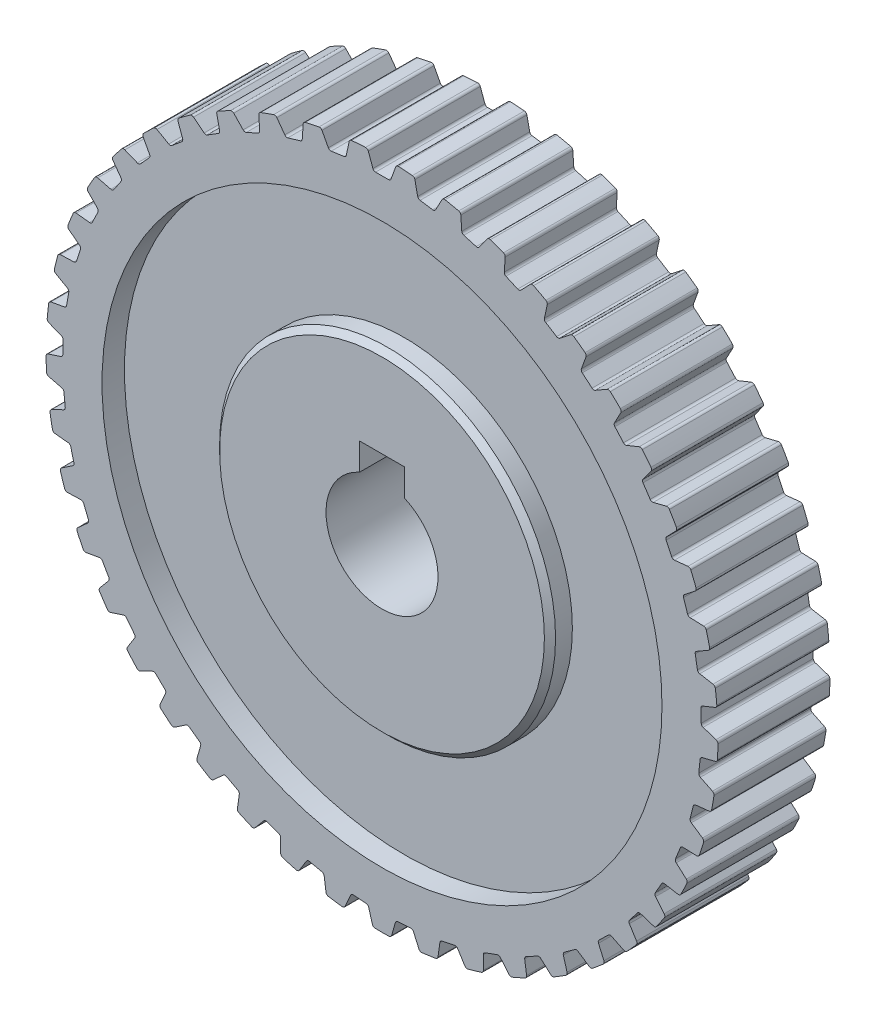
SolidWorks part; units mm, degrees
material "Alloy Steel (SS)"
ref_plane "Front " through (0, 0, 0) normal (0, 0, 1) x (1, 0, 0)
ref_plane "Top " through (0, 0, 0) normal (0, 1, 0) x (1, 0, 0)
ref_plane "Right " through (0, 0, 0) normal (1, 0, 0) x (0, 0, -1)
sketch "Sketch1" plane through (0, 0, 0) normal (0, 0, 1) x (1, 0, 0)
  line L0 (0, 0) -> (0, 14.3078) construction
  line L2 (2, 7) -> (-2, 7)
  line L3 (2, 7) -> (2, 4.5826)
  line L5 (-2, 7) -> (-2, 4.5826)
  circle A0 centre (0, 0) radius 30
  arc A1 (-2, 4.5826) -> (2, 4.5826) centre (0, 0) ccw
  dimension "D1" = 60
  dimension "D2" = 10
  dimension "D3" = 4
  dimension "D4" = 7
extrude "Boss-Extrude1" add sketch "Sketch1" along normal blind 10
sketch "Sketch2" plane through (0, 0, 10) normal (0, 0, 1) x (1, 0, 0)
  line L0 (0, 0) -> (0, 30) construction
  line L1 (-0.75, 28.5) -> (0.75, 28.5)
  line L2 (0.75, 28.5) -> (1.2859, 29.9724)
  line L3 (-0.75, 28.5) -> (-1.2859, 29.9724)
  circle A0 centre (0, 0) radius 30 construction
  circle A1 centre (0, 0) radius 30
  circle M5 centre (0, 0) radius 30
  dimension "D1" = 20
  dimension "D2" = 20
  dimension "D3" = 1.5
  dimension "D4" = 28.5
extrude "Cut-Extrude1" cut sketch "Sketch2" against normal through all contours L1 L0 A1 L3 | L0 L1 L2 M5 region at (-0.5201, 29.3114, 10) region at (0.5201, 29.3114, 10)
pattern_circular "CirPattern1" count 45 over 360 about axis through (0, 0, 10) along (0, 0, 1) of "Cut-Extrude1"
sketch "Sketch3" plane through (0, 0, 10) normal (0, 0, 1) x (1, 0, 0)
  circle A0 centre (0, 0) radius 25
  dimension "D1" = 50
extrude "Cut-Extrude-Thin1" cut sketch "Sketch3" against normal blind 2 thin thin type one direction reverse wall 10
chamfer "Chamfer1" distance 0.5 angle 45 1 edges at (15, 0, 10)
ref_plane "Plane1" through (0, 0, 5) normal (0, 0, 1) x (1, 0, 0)
mirror "Mirror1" about plane through (0, 0, 5) normal (0, 0, 1) of "Cut-Extrude-Thin1"
chamfer "Chamfer2" distance 0.5 angle 45 1 edges at (15, 0, 0)
fillet "Fillet1" radius 0.25 180 edges at (29.9427, -1.8541, 5) (29.999, -0.2391, 5) (28.5088, 0.2451, 5) (28.4565, 1.7442, 5) (29.9093, 2.3312, 5) (29.7404, 3.9383, 5) (28.1973, 4.2104, 5) (27.9368, 5.6876, 5) (29.2938, 6.471, 5) (28.9028, 8.039, 5) (27.3369, 8.0937, 5) (26.8733, 9.5203, 5) (28.1081, 10.485, 5) (27.5027, 11.9833, 5) (25.9444, 11.8195, 5) (25.2869, 13.1677, 5) (26.3753, 14.2948, 5) (25.5673, 15.6943, 5) (24.047, 15.3152, 5) (23.2082, 16.5588, 5) (24.1292, 17.8264, 5) (23.1343, 19.0998, 5) (21.6815, 18.5129, 5) (20.6778, 19.6276, 5) (21.4134, 21.0111, 5) (20.251, 22.1336, 5) (18.894, 21.3502, 5) (17.7449, 22.3144, 5) (18.2808, 23.7868, 5) (16.9735, 24.7366, 5) (15.7387, 23.7719, 5) (14.4667, 24.5668, 5) (14.7924, 26.0995, 5) (13.3656, 26.8581, 5) (12.2772, 25.731, 5) (10.9068, 26.3411, 5) (11.0161, 27.9042, 5) (9.4976, 28.4569, 5) (8.5766, 27.1892, 5) (7.1347, 27.6027, 5) (5.4448, 29.5018, 5) (4.7091, 28.1183, 5) (3.2237, 28.327, 5) (2.898, 29.8597, 5) (1.2859, 29.9724, 5) (0.75, 28.5, 5) (-0.75, 28.5, 5) (-1.2859, 29.9724, 5) (-2.898, 29.8597, 5) (-3.2237, 28.327, 5) (-4.7091, 28.1183, 5) (-5.4448, 29.5018, 5) (-7.0254, 29.1658, 5) (-7.1347, 27.6027, 5) (-8.5766, 27.1892, 5) (-9.4976, 28.4569, 5) (-11.0161, 27.9042, 5) (-10.9068, 26.3411, 5) (-12.2772, 25.731, 5) (-13.3656, 26.8581, 5) (-14.7924, 26.0995, 5) (-14.4667, 24.5668, 5) (-15.7387, 23.7719, 5) (-16.9735, 24.7366, 5) (-18.2808, 23.7868, 5) (-17.7449, 22.3144, 5) (-18.894, 21.3502, 5) (-20.251, 22.1336, 5) (-21.4134, 21.0111, 5) (-20.6778, 19.6276, 5) (-21.6815, 18.5129, 5) (-23.1343, 19.0998, 5) (-24.1292, 17.8264, 5) (-23.2082, 16.5588, 5) (-24.047, 15.3152, 5) (-25.5673, 15.6943, 5) (-26.3753, 14.2948, 5) (-25.2869, 13.1677, 5) (-25.9444, 11.8195, 5) (-27.5027, 11.9833, 5) (-28.1081, 10.485, 5) (-26.8733, 9.5203, 5) (-27.3369, 8.0937, 5) (-28.9028, 8.039, 5) (-29.2938, 6.471, 5) (-27.9368, 5.6876, 5) (-28.1973, 4.2104, 5) (-29.7404, 3.9383, 5) (-29.9093, 2.3312, 5) (-28.4565, 1.7442, 5) (-28.5088, 0.2451, 5) (-29.999, -0.2391, 5) (-29.9427, -1.8541, 5) (-28.4223, -2.2332, 5) (-28.2655, -3.725, 5) (-29.6738, -4.4118, 5) (-29.3932, -6.0033, 5) (-27.8349, -6.1671, 5) (-27.472, -7.6225, 5) (-28.771, -8.4987, 5) (-28.2717, -10.0356, 5) (-26.7057, -9.9809, 5) (-26.1438, -11.3717, 5) (-27.3082, -12.4202, 5) (-26.5998, -13.8726, 5) (-25.0567, -13.6005, 5) (-24.3067, -14.8995, 5) (-25.3139, -16.0999, 5) (-24.4103, -17.4396, 5) (-22.9201, -16.9553, 5) (-21.9966, -18.1374, 5) (-22.8269, -19.4662, 5) (-21.7456, -20.6671, 5) (-20.3373, -19.9802, 5) (-19.2583, -21.0222, 5) (-19.8956, -22.4536, 5) (-18.6577, -23.4924, 5) (-17.3586, -22.6161, 5) (-16.1451, -23.4978, 5) (-16.577, -25.004, 5) (-15.2066, -25.8604, 5) (-14.0422, -24.8119, 5) (-12.7177, -25.5161, 5) (-12.9358, -27.0678, 5) (-11.4595, -27.7251, 5) (-10.4523, -26.5247, 5) (-9.0428, -27.0378, 5) (-9.0428, -28.6047, 5) (-7.4894, -29.0501, 5) (-6.6591, -27.7213, 5) (-5.1919, -28.0331, 5) (-4.9738, -29.5848, 5) (-3.3736, -29.8097, 5) (-2.7362, -28.3783, 5) (-1.2399, -28.4829, 5) (-0.808, -29.9891, 5) (0.808, -29.9891, 5) (1.2399, -28.4829, 5) (2.7362, -28.3783, 5) (3.3736, -29.8097, 5) (4.9738, -29.5848, 5) (5.1919, -28.0331, 5) (6.6591, -27.7213, 5) (7.4894, -29.0501, 5) (9.0428, -28.6047, 5) (9.0428, -27.0378, 5) (10.4523, -26.5247, 5) (11.4595, -27.7251, 5) (12.9358, -27.0678, 5) (12.7177, -25.5161, 5) (14.0422, -24.8119, 5) (15.2066, -25.8604, 5) (16.577, -25.004, 5) (16.1451, -23.4978, 5) (17.3586, -22.6161, 5) (18.6577, -23.4924, 5) (19.8956, -22.4536, 5) (19.2583, -21.0222, 5) (20.3373, -19.9802, 5) (21.7456, -20.6671, 5) (22.8269, -19.4662, 5) (21.9966, -18.1374, 5) (22.9201, -16.9553, 5) (24.4103, -17.4396, 5) (25.3139, -16.0999, 5) (24.3067, -14.8995, 5) (25.0567, -13.6005, 5) (26.5998, -13.8726, 5) (27.3082, -12.4202, 5) (26.1438, -11.3717, 5) (26.7057, -9.9809, 5) (28.2717, -10.0356, 5) (28.771, -8.4987, 5) (27.472, -7.6225, 5) (27.8349, -6.1671, 5) (29.3932, -6.0033, 5) (29.6738, -4.4118, 5) (28.2655, -3.725, 5) (28.4223, -2.2332, 5) (7.0254, 29.1658, 5)
